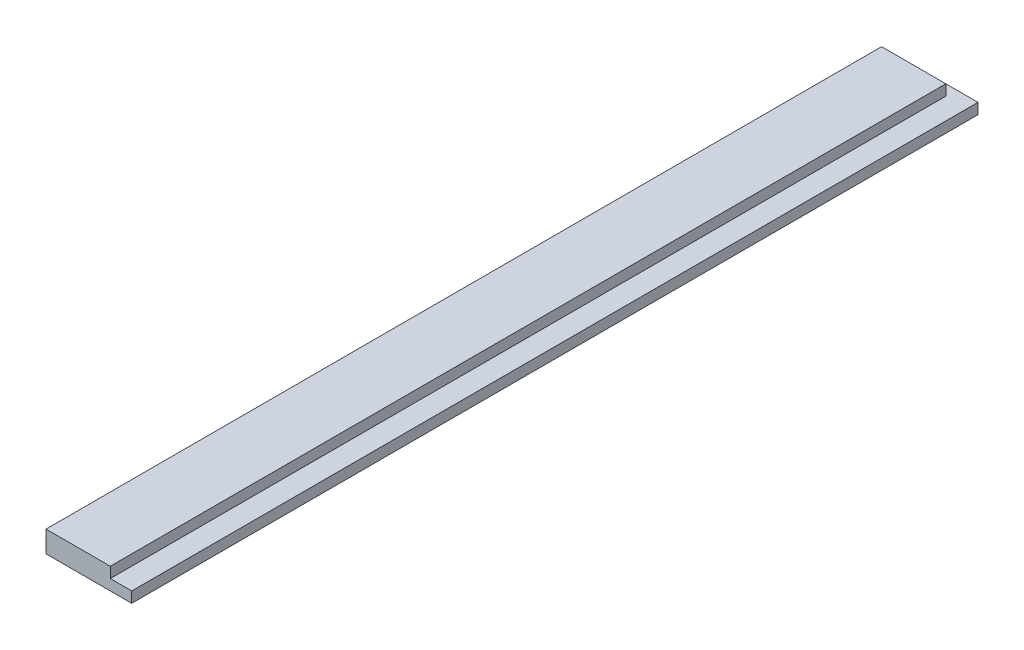
SolidWorks part; units mm, degrees
ref_plane "Front Plane" through (0, 0, 0) normal (0, 0, 1) x (1, 0, 0)
ref_plane "Top Plane" through (0, 0, 0) normal (0, 1, 0) x (1, 0, 0)
ref_plane "Right Plane" through (0, 0, 0) normal (1, 0, 0) x (0, 0, -1)
sketch "Sketch1" plane through (0, 0, 0) normal (0, 0, 1) x (1, 0, 0)
  line L0 (0, 12.7) -> (38.1, 12.7)
  line L1 (38.1, 12.7) -> (38.1, 6.35)
  line L2 (38.1, 6.35) -> (50.8, 6.35)
  line L3 (50.8, 6.35) -> (50.8, 0)
  line L4 (50.8, 0) -> (0, 0)
  line L5 (0, 0) -> (0, 12.7)
  dimension "D1" = 6.35
  dimension "D2" = 6.35
  dimension "D3" = 50.8
  dimension "D4" = 12.7
extrude "Boss-Extrude1" add sketch "Sketch1" along normal blind 501.65
sketch "Sketch3" plane through (0, 12.7, 0) normal (0, 1, 0) x (1, 0, 0)
  line L0 (38.1, -501.65) -> (38.1, 0) construction
  line L1 (38.1, -6.35) -> (0, -6.35)
  line L2 (38.1, -6.35) -> (38.1, 0)
  line L3 (38.1, 0) -> (0, 0)
  line L4 (0, -6.35) -> (0, 0)
  dimension "D1" = 6.35
extrude "Cut-Extrude1" cut sketch "Sketch3" against normal blind 6.35
